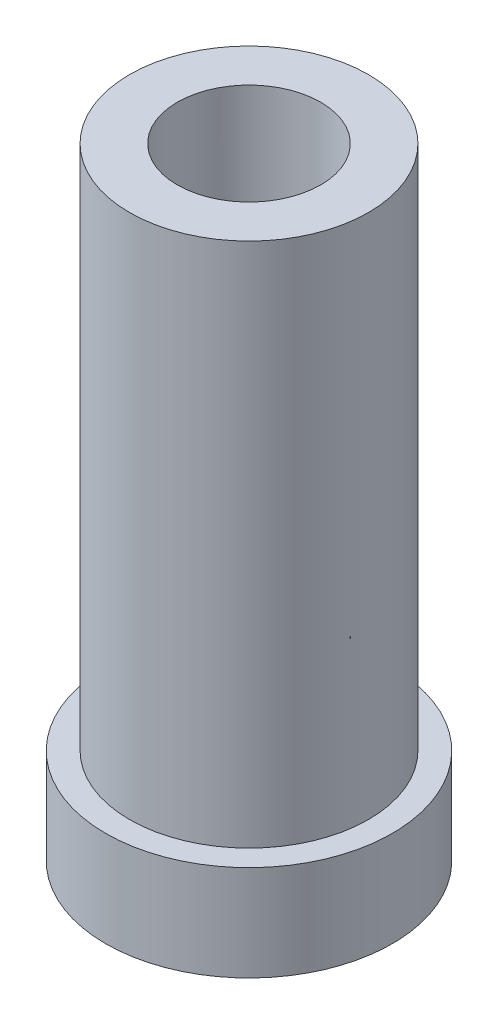
SolidWorks part; units mm, degrees
ref_plane "Front Plane" through (0, 0, 0) normal (0, 0, 1) x (1, 0, 0)
ref_plane "Top Plane" through (0, 0, 0) normal (0, 1, 0) x (1, 0, 0)
ref_plane "Right Plane" through (0, 0, 0) normal (1, 0, 0) x (0, 0, -1)
sketch "Sketch1" plane through (0, 0, 0) normal (0, 1, 0) x (1, 0, 0)
  circle A0 centre (0, 0) radius 1.5
  circle A1 centre (0, 0) radius 2.5
  dimension "D1" = 3
  dimension "D2" = 5
extrude "Boss-Extrude1" add sketch "Sketch1" along normal blind 11
sketch "Sketch2" plane through (0, 0, 0) normal (0, -1, 0) x (-1, 0, 0)
  circle A0 centre (0, 0) radius 3
  dimension "D1" = 6
extrude "Boss-Extrude2" add sketch "Sketch2" along normal blind 2
sketch "Sketch3" plane through (0, -2, 0) normal (0, -1, 0) x (-1, 0, 0)
  circle A0 centre (0, 0) radius 1.5
  dimension "D1" = 3
extrude "Cut-Extrude1" cut sketch "Sketch3" against normal through all
